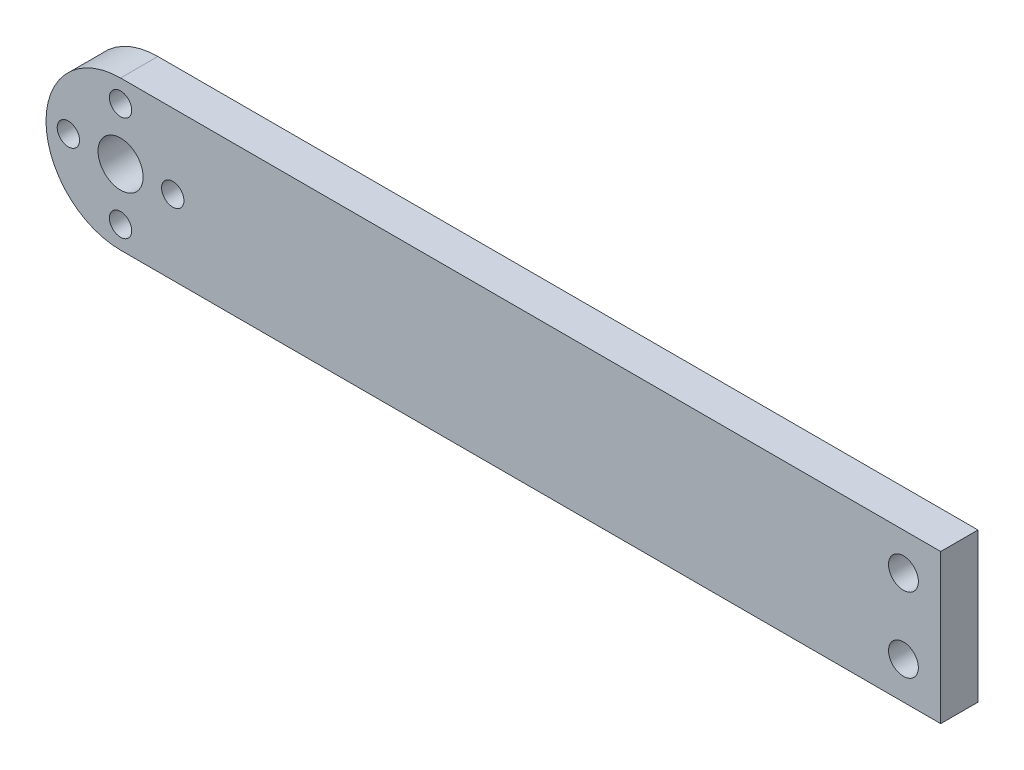
SolidWorks part; units mm, degrees
ref_plane "Front Plane" through (0, 0, 0) normal (0, 0, 1) x (1, 0, 0)
ref_plane "Top Plane" through (0, 0, 0) normal (0, 1, 0) x (1, 0, 0)
ref_plane "Right Plane" through (0, 0, 0) normal (1, 0, 0) x (0, 0, -1)
sketch "Sketch1" plane through (0, 0, 0) normal (0, 0, 1) x (1, 0, 0)
  line L1 (0, 0) -> (120, 0)
  line L2 (0, 0) -> (0, 20)
  line L3 (0, 20) -> (120, 20)
  line L4 (120, 0) -> (120, 20)
  dimension "D1" = 20
  dimension "D2" = 120
extrude "Boss-Extrude1" add sketch "Sketch1" along normal blind 5
sketch "Sketch2" plane through (0, 0, 5) normal (0, 0, 1) x (1, 0, 0)
  line L0 (10, 27.53) -> (10, -7.53) construction
  line L1 (-17.6366, 10) -> (37.6366, 10) construction
  line L2 (0, 20) -> (0, 0) construction
  circle A0 centre (10, 17) radius 1.5
  circle A1 centre (10, 10) radius 3.025
  circle A2 centre (10, 10) radius 3.025
  circle A3 centre (17, 10) radius 1.5
  circle A4 centre (10, 10) radius 3.025
  circle A5 centre (10, 3) radius 1.5
  circle A6 centre (10, 10) radius 3.025
  circle A7 centre (3, 10) radius 1.5
  point P4 (10, 10)
  point P5 (10, 10)
  point P8 (0, 10)
  point P14 (10, 10)
  point P15 (19.563, 12.9237)
  point P25 (10, 10)
  point P30 (30, 10)
  line M11 (0, 20) -> (0, 0)
  line M12 (0, 0) -> (120, 0)
  line M14 (120, 20) -> (0, 20)
  dimension "D1" = 10
  dimension "D2" = 3
  dimension "D4" = 6.05
  dimension "D3" = 7
  dimension "D5" = 4
extrude "Cut-Extrude1" cut sketch "Sketch2" against normal blind 10 contours A0 | A7 | A1 | A3 | M12 M11 M14 | A5 region at (10, 17, 5) region at (10, 10, 5) region at (17, 10, 5) region at (3, 10, 5)
sketch "Sketch3" plane through (0, 0, 5) normal (0, 0, 1) x (1, 0, 0)
  line L0 (10, 30) -> (10, 20)
  line L1 (10, 0) -> (10, -10)
  arc A0 (10, 20) -> (10, 0) centre (10, 10) ccw
  arc A1 (10, 30) -> (10, -10) centre (10, 10) ccw
  circle A3 centre (10, 10) radius 10 construction
  circle A4 centre (10, 10) radius 20 construction
  point P1 (30, 10)
  point P9 (19.563, 12.9237)
  dimension "D1" = 10
  dimension "D2" = 20
extrude "Cut-Extrude2" cut sketch "Sketch3" against normal blind 10
sketch "Sketch5" plane through (0, 0, 5) normal (0, 0, 1) x (1, 0, 0)
  line L0 (120, 0) -> (120, 20) construction
  line L1 (120, 10) -> (88.8314, 10) construction
  circle A0 centre (115, 15) radius 2
  circle A1 centre (115, 5) radius 2
  point P2 (120, 10)
  dimension "D1" = 5
  dimension "D2" = 4
  dimension "D3" = 4
  dimension "D4" = 5
  dimension "D5" = 5
extrude "Cut-Extrude3" cut sketch "Sketch5" against normal blind 10
